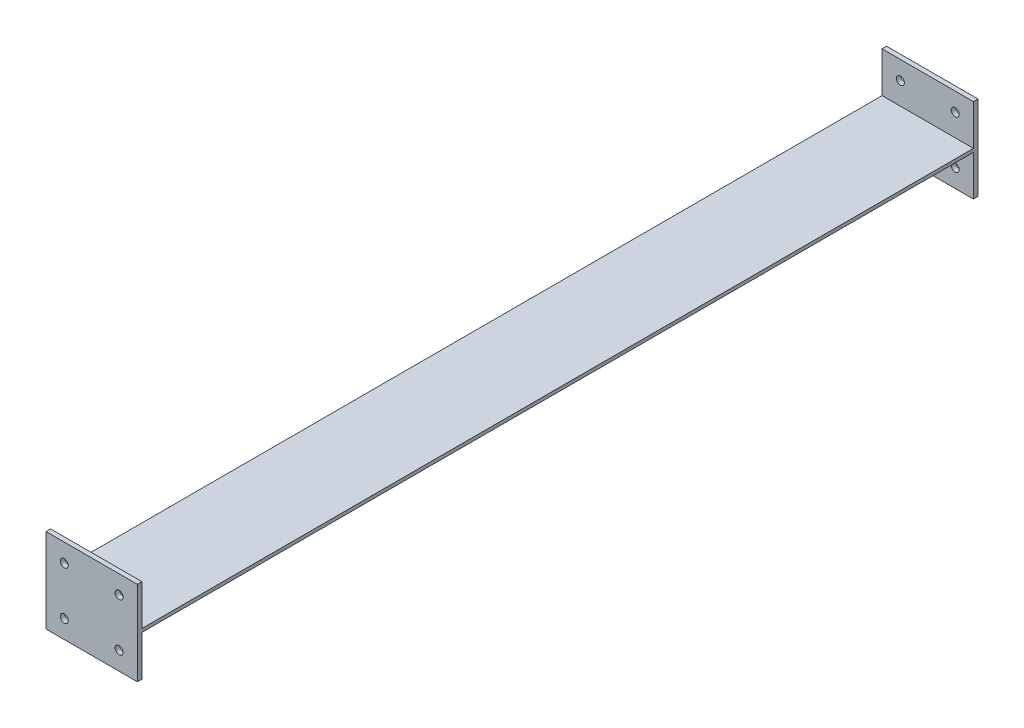
SolidWorks part; units mm, degrees
material "Galvanized Steel"
ref_plane "Front Plane" through (0, 0, 0) normal (0, 0, 1) x (1, 0, 0)
ref_plane "Top Plane" through (0, 0, 0) normal (0, 1, 0) x (1, 0, 0)
ref_plane "Right Plane" through (0, 0, 0) normal (1, 0, 0) x (0, 0, -1)
sketch "Sketch1" plane through (0, 0, 0) normal (0, 0, 1) x (1, 0, 0)
  line L1 (0, 0) -> (127, 0)
  line L2 (0, 0) -> (0, 117.348)
  line L3 (0, 117.348) -> (127, 117.348)
  line L4 (127, 0) -> (127, 117.348)
  dimension "D1" = 127
  dimension "D2" = 117.348
extrude "Boss-Extrude1" add sketch "Sketch1" against normal blind 6.35
sketch "Sketch2" plane through (0, 0, -6.35) normal (0, 0, -1) x (-1, 0, 0)
  line L0 (-127, 0) -> (-127, 117.348) construction
  line L1 (-127, 56.2927) -> (0, 56.2927)
  line L2 (-127, 56.2927) -> (-127, 61.0553)
  line L3 (-127, 61.0553) -> (0, 61.0553)
  line L4 (0, 56.2927) -> (0, 61.0553)
  line L5 (0, 117.348) -> (0, 0) construction
  point P8 (-127, 58.674)
  dimension "D1" = 4.7625
extrude "Boss-Extrude2" add sketch "Sketch2" along normal blind 1155.7
sketch "Sketch3" plane through (0, 0, -1162.05) normal (0, 0, -1) x (-1, 0, 0)
  line L1 (-127, 117.348) -> (0, 117.348)
  line L2 (-127, 117.348) -> (-127, 0)
  line L3 (-127, 0) -> (0, 0)
  line L4 (0, 117.348) -> (0, 0)
extrude "Boss-Extrude3" add sketch "Sketch3" along normal blind 6.35
sketch "Sketch4" plane through (0, 0, -1168.4) normal (0, 0, -1) x (-1, 0, 0)
  line L0 (0, 117.348) -> (-127, 117.348) construction
  line L1 (-127, 117.348) -> (-127, 0) construction
  line L2 (-127, 0) -> (0, 0) construction
  line L3 (0, 0) -> (0, 117.348) construction
  circle A0 centre (-101.6, 91.948) radius 5.5563
  circle A1 centre (-25.4, 91.948) radius 5.5562
  circle A2 centre (-25.4, 25.4) radius 5.5562
  circle A3 centre (-101.6, 25.4) radius 5.5563
  dimension "D1" = 11.1125
  dimension "D2" = 25.4
  dimension "D3" = 25.4
  dimension "D4" = 25.4
  dimension "D5" = 25.4
extrude "Cut-Extrude1" cut sketch "Sketch4" against normal blind 1168.4
